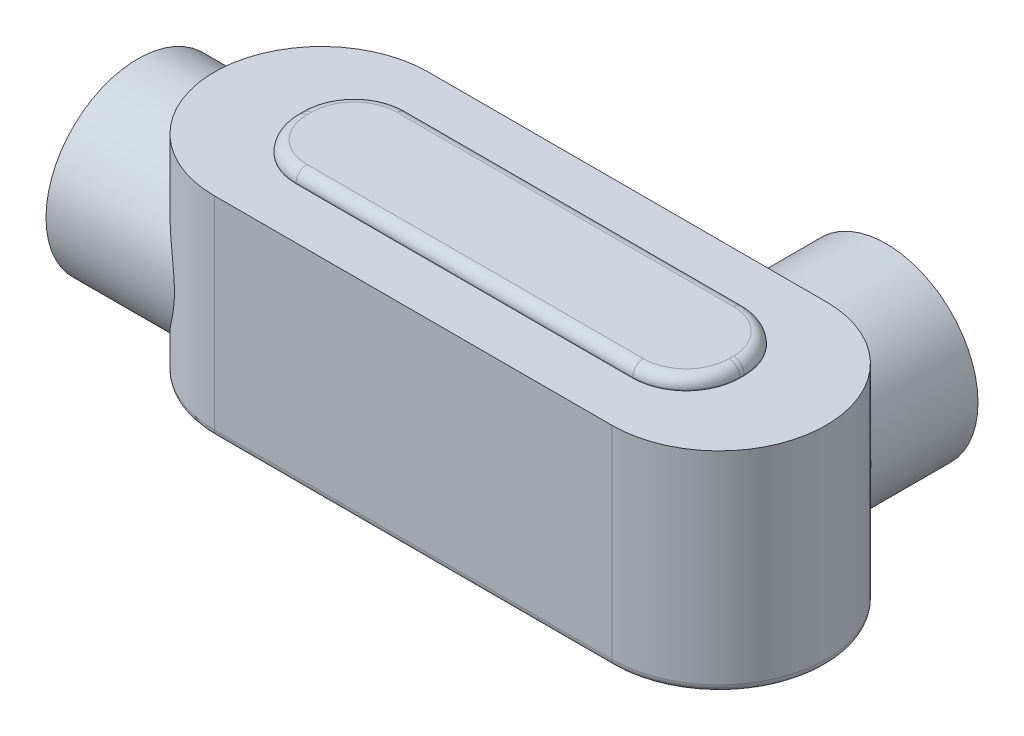
SolidWorks part; units mm, degrees
ref_plane "Alzado" through (0, 0, 0) normal (0, 0, 1) x (1, 0, 0)
ref_plane "Planta" through (0, 0, 0) normal (0, 1, 0) x (1, 0, 0)
ref_plane "Vista lateral" through (0, 0, 0) normal (1, 0, 0) x (0, 0, -1)
sketch "Croquis1" plane through (0, 0, 0) normal (0, 0, 1) x (1, 0, 0)
  line L1 (0, 0) -> (80, 0)
  line L2 (0, 0) -> (0, -29)
  line L3 (0, -29) -> (80, -29)
  line L4 (80, 0) -> (80, -29)
  dimension "D1" = 80
  dimension "D2" = 29
extrude "Saliente-Extruir1" add sketch "Croquis1" along normal blind 28
sketch "Croquis5" plane through (0, 0, 0) normal (0, 1, 0) x (1, 0, 0)
  line L0 (0, -14) -> (14, -14) construction
  line L1 (0, -28) -> (0, 0) construction
  line L2 (14, 0) -> (14, 3.8547)
  line L3 (14, 3.8547) -> (-5.025, 3.8547)
  line L4 (-5.025, 3.8547) -> (-5.025, -14)
  line L5 (-5.025, -14) -> (-5.025, -30.4747)
  line L6 (-5.025, -30.4747) -> (14, -30.4747)
  line L7 (14, -30.4747) -> (14, -28)
  line L8 (40, 0) -> (40, -28) construction
  line L9 (80, 0) -> (0, 0) construction
  line L10 (80, -28) -> (0, -28) construction
  line L11 (80, -14) -> (66, -14) construction
  line L12 (66, -30.4747) -> (66, -28)
  line L13 (85.025, -30.4747) -> (66, -30.4747)
  line L14 (85.025, -14) -> (85.025, -30.4747)
  line L15 (85.025, 3.8547) -> (85.025, -14)
  line L16 (66, 3.8547) -> (85.025, 3.8547)
  line L17 (66, 0) -> (66, 3.8547)
  arc A0 (14, 0) -> (14, -28) centre (14, -14) ccw
  arc A1 (66, 0) -> (66, -28) centre (66, -14) cw
  dimension "D1" = 14
extrude "Cortar-Extruir1" cut sketch "Croquis5" against normal up to surface (29 mm away) up to face at (40, -29, 14)
sketch "Croquis6" plane through (0, 0, 0) normal (1, 0, 0) x (0, 0, -1)
  line L0 (-14, -29) -> (-14, -17) construction
  line L1 (-28, -29) -> (0, -29) construction
  circle A0 centre (-14, -17) radius 12
  circle A1 centre (-14, -17) radius 7
  dimension "D2" = 14
  dimension "D1" = 12
extrude "Saliente-Extruir5" add sketch "Croquis6" along normal blind 60
sketch "Croquis7" plane through (0, 0, 0) normal (-1, 0, 0) x (0, 0, 1)
  circle A0 centre (14, -17) radius 7
  circle A1 centre (14, -17) radius 12
extrude "Saliente-Extruir6" add sketch "Croquis7" along normal blind 10
fillet "Redondeo7" radius 1 5 edges at (4.1005, -29, 4.1005) (40, -29, 0) (80, -29, 14) (40, -29, 28) (4.1005, -29, 23.8995)
sketch "Croquis9" plane through (0, 0, 0) normal (0, 1, 0) x (1, 0, 0)
  line L0 (40, 0) -> (40, -28) construction
  line L1 (66, 0) -> (14, 0) construction
  line L2 (66, -28) -> (14, -28) construction
  line L4 (62.0032, -21.2913) -> (17.9968, -21.2913)
  line L5 (69.0032, -14.2913) -> (69.0032, -13.7087)
  line L6 (62.0032, -6.7087) -> (17.9968, -6.7087)
  line L7 (10.9968, -14.2913) -> (10.9968, -13.7087)
  line L8 (69.0032, -21.2913) -> (10.9968, -6.7087) construction
  line L9 (69.0032, -6.7087) -> (10.9968, -21.2913) construction
  line L10 (-1.8336, -29.7012) -> (81.8336, -29.7012)
  line L11 (-1.8336, -29.7012) -> (-1.8336, 1.7012)
  line L12 (-1.8336, 1.7012) -> (81.8336, 1.7012)
  line L13 (81.8336, -29.7012) -> (81.8336, 1.7012)
  line L14 (-1.8336, -29.7012) -> (81.8336, 1.7012) construction
  line L15 (-1.8336, 1.7012) -> (81.8336, -29.7012) construction
  arc A0 (62.0032, -21.2913) -> (69.0032, -14.2913) centre (62.0032, -14.2913) ccw
  arc A1 (69.0032, -13.7087) -> (62.0032, -6.7087) centre (62.0032, -13.7087) ccw
  arc A2 (17.9968, -21.2913) -> (10.9968, -14.2913) centre (17.9968, -14.2913) cw
  arc A3 (17.9968, -6.7087) -> (10.9968, -13.7087) centre (17.9968, -13.7087) ccw
  point P6 (40, -14)
  point P23 (40, -14)
  dimension "D1" = 7
extrude "Cortar-Extruir2" cut sketch "Croquis9" against normal blind 1.5
fillet "Redondeo9" radius 1.4 8 edges at (10.9968, 0, 14) (13.0471, 0, 8.7589) (40, 0, 6.7087) (66.9529, 0, 8.7589) (69.0032, 0, 14) (66.9529, 0, 19.2411) (40, 0, 21.2913) (13.0471, 0, 19.2411)
sketch "Croquis10" plane through (0, 0, 0) normal (0, 0, -1) x (-1, 0, 0)
  line L0 (10, -17) -> (-66, -17) construction
  line L2 (10, -29) -> (10, -5) construction
  line L3 (-66, -28) -> (-66, -1.5) construction
  circle A0 centre (-59.8618, -17) radius 12
extrude "Saliente-Extruir7" add sketch "Croquis10" along normal blind 14
scale "Escala1" scale about centroid uniform scaling yes scale factor 1.3
